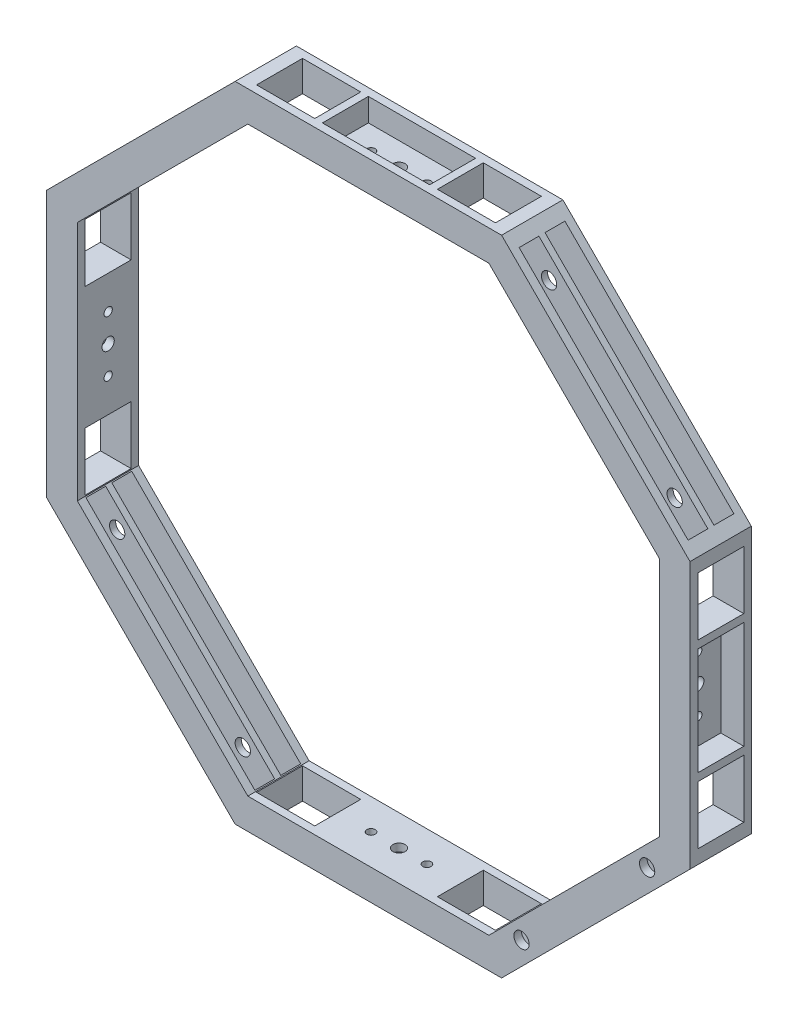
SolidWorks part; units mm, degrees
ref_plane "Plano frontal" through (0, 0, 0) normal (0, 0, 1) x (1, 0, 0)
ref_plane "Plano superior" through (0, 0, 0) normal (0, 1, 0) x (1, 0, 0)
ref_plane "Plano direito" through (0, 0, 0) normal (1, 0, 0) x (0, 0, -1)
sketch "Esboço1" plane through (0, 0, 0) normal (0, 0, 1) x (1, 0, 0)
  line L9 (210, 86.9848) -> (86.9848, 210)
  line L10 (86.9848, 210) -> (-86.9848, 210)
  line L11 (-86.9848, 210) -> (-210, 86.9848)
  line L12 (-210, 86.9848) -> (-210, -86.9848)
  line L13 (-210, -86.9848) -> (-86.9848, -210)
  line L14 (-86.9848, -210) -> (86.9848, -210)
  line L15 (86.9848, -210) -> (210, -86.9848)
  line L16 (210, -86.9848) -> (210, 86.9848)
  line L17 (190, 78.7006) -> (78.7006, 190)
  line L18 (78.7006, 190) -> (-78.7006, 190)
  line L19 (-78.7006, 190) -> (-190, 78.7006)
  line L20 (-190, 78.7006) -> (-190, -78.7006)
  line L21 (-190, -78.7006) -> (-78.7006, -190)
  line L22 (-78.7006, -190) -> (78.7006, -190)
  line L23 (78.7006, -190) -> (190, -78.7006)
  line L24 (190, -78.7006) -> (190, 78.7006)
  circle A0 centre (0, 0) radius 210 construction
  circle A1 centre (0, 0) radius 190 construction
extrude "Ressalto-extrusão1" add sketch "Esboço1" along normal blind 40
sketch "Esboço2" plane through (210, 0, 0) normal (1, 0, 0) x (0, 0, -1)
  line L1 (-4.9012, 78) -> (-4.9012, -78)
  line L23 (-4.9012, 78) -> (-34.9012, 78)
  line L24 (-34.9012, 78) -> (-34.9012, -78)
  line L25 (-4.9012, -78) -> (-34.9012, -78)
  line L26 (-4.9012, 78) -> (-4.9012, -78)
  line L27 (-4.9012, 78) -> (-34.9012, 78)
  line L28 (-34.9012, 78) -> (-34.9012, -78)
  line L29 (-4.9012, -78) -> (-34.9012, -78)
  line L30 (-4.9012, 0) -> (-4.9012, -40.0505)
  line L31 (-34.9012, 0) -> (-34.9012, -40.0505)
  line L32 (-4.9012, -40.0505) -> (-34.9012, -40.0505)
  line L33 (-4.9012, 0) -> (-4.9012, 40)
  line L34 (-34.9012, 0) -> (-34.9012, 40)
  line L35 (-4.9012, 40) -> (-34.9012, 40)
  line L36 (-4.9012, 35) -> (-4.9012, -35)
  line L37 (-4.9012, 35) -> (-34.9012, 35)
  line L38 (-34.9012, 35) -> (-34.9012, -35)
  line L39 (-4.9012, -35) -> (-34.9012, -35)
  circle A0 centre (-19.9012, 0) radius 4
  circle A1 centre (-19.9012, -18.25) radius 2.7
  circle A2 centre (-19.9012, 18.25) radius 2.7
extrude "Corte-extrusão2" cut sketch "Esboço2" against normal up to next and the other way through all contours L1 L32 L24 L25 | A0 | A2 | A1 | L35 L1 L23 L24 region at (210, 59, 19.9012) region at (210, -59.0253, 19.9012) region at (210, 0, 19.9012) region at (210, -18.25, 19.9012) region at (210, 18.25, 19.9012)
sketch "Esboço15" plane through (-148.4924, 148.4924, 0) normal (-0.7071, 0.7071, 0) x (0, 0, 1)
  line L0 (40, 86.9848) -> (0, 86.9848) construction
  line L1 (5, 86.9848) -> (35, 86.9848)
  line L2 (5, 86.9848) -> (5, -86.9848)
  line L3 (5, -86.9848) -> (35, -86.9848)
  line L4 (35, 86.9848) -> (35, -86.9848)
  line L5 (40, -86.9848) -> (0, -86.9848) construction
  line L9 (20, 86.9848) -> (22, 86.9848)
  line L11 (20, -86.9848) -> (22, -86.9848)
  line L12 (22, 78) -> (22, -78)
  line L14 (20, 86.9848) -> (18, 86.9848)
  line L16 (20, -86.9848) -> (18, -86.9848)
  line L17 (18, 78) -> (18, -78)
  line L19 (5, 86.9848) -> (35, 86.9848)
  line L20 (5, 86.9848) -> (5, 78)
  line L21 (5, 78) -> (35, 78)
  line L22 (35, 86.9848) -> (35, 78)
  line L24 (5, -86.9848) -> (35, -86.9848)
  line L25 (5, -86.9848) -> (5, -78)
  line L26 (5, -78) -> (35, -78)
  line L27 (35, -86.9848) -> (35, -78)
extrude "Corte-extrusão5" cut sketch "Esboço15" against normal up to next contours L12 L26 L4 L21 | L2 L26 L17 L21 region at (-148.4924, 148.4924, 11.5) region at (-148.4924, 148.4924, 28.5)
sketch "Esboço16" plane through (148.4924, 148.4924, 0) normal (0.7071, 0.7071, 0) x (0, 0, -1)
  line L0 (-40, 86.9848) -> (0, 86.9848) construction
  line L2 (-34.9012, -78) -> (-34.9012, 86.9848)
  line L3 (-34.9012, 86.9848) -> (-5, 86.9848)
  line L4 (-5, -86.8738) -> (-5, 86.9848)
  line L8 (-34.9012, -78) -> (-5, -78)
  line L9 (-5, -86.8738) -> (-5, -78)
  line L10 (-5, 86.9848) -> (-34.9012, 86.9848)
  line L11 (-5, 86.9848) -> (-5, 78)
  line L12 (-5, 78) -> (-34.9012, 78)
  line L13 (-34.9012, 86.9848) -> (-34.9012, 78)
  line L14 (-19.9506, 78) -> (-18, 78)
  line L16 (-20, -78) -> (-18, -78)
  line L17 (-18, 78) -> (-18, -78)
  line L18 (-20, -78) -> (-22, -78)
  line L20 (-19.9506, 78) -> (-22, 78)
  line L21 (-22, -78) -> (-22, 78)
  line L22 (-34.9012, -78) -> (-5, -78)
  line L23 (-34.9012, -78) -> (-34.9012, -86.8738)
  line L24 (-34.9012, -86.8738) -> (-5, -86.8738)
  line L25 (-5, -78) -> (-5, -86.8738)
extrude "Corte-extrusão6" cut sketch "Esboço16" against normal through all both and the other way through all contours L8 L21 L12 L2 | L12 L17 L8 L4 region at (148.4924, 148.4924, 28.4506) region at (148.4924, 148.4924, 11.5)
sketch "Esboço18" plane through (0, -210, 0) normal (0, -1, 0) x (1, 0, 0)
  line L1 (-78, 35) -> (78, 35)
  line L2 (-78, 35) -> (-78, 5)
  line L3 (-78, 5) -> (78, 5)
  line L4 (78, 35) -> (78, 5)
  line L5 (-78, 35) -> (78, 35)
  line L6 (-78, 35) -> (-78, 5)
  line L7 (-78, 5) -> (78, 5)
  line L8 (78, 35) -> (78, 5)
  line L9 (0, 35) -> (40.0505, 35)
  line L11 (0, 5) -> (40.0505, 5)
  line L12 (40.0505, 35) -> (40.0505, 5)
  line L13 (0, 35) -> (-40, 35)
  line L15 (0, 5) -> (-40, 5)
  line L16 (-40, 35) -> (-40, 5)
  line L17 (-35, 35) -> (35, 35)
  line L18 (-35, 35) -> (-35, 5)
  line L19 (-35, 5) -> (35, 5)
  line L20 (35, 35) -> (35, 5)
  circle A0 centre (0, 20) radius 4
  circle A1 centre (18.25, 20) radius 2.7
  circle A2 centre (-18.25, 20) radius 2.7
  line M8 (86.9848, 0) -> (86.9848, 40)
  line M12 (-86.9848, 40) -> (-86.9848, 0)
sketch "Esboço26" plane through (0, 0, 0) normal (0, 0, -1) x (-1, 0, 0)
  circle A0 centre (100, 182) radius 5
  circle A1 centre (182, 100) radius 5
  circle A2 centre (-182, -100) radius 5
  circle A3 centre (-100, -182) radius 5
  circle A4 centre (100, -182) radius 5
  circle A5 centre (182, -100) radius 5
  circle A6 centre (-182, 100) radius 5
  circle A7 centre (-100, 182) radius 5
  point P16 (0, 0)
extrude "Corte-extrusão10" cut sketch "Esboço26" against normal up to next from surface starting at face at (141.4214, 141.4214, 18)
extrude "Corte-extrusão12" cut sketch "Esboço18" against normal through all contours L16 L1 L3 M12 | L1 L12 L3 M8 | A2 | A0 | A1 region at (-59, -210, 20) region at (59.0253, -210, 20) region at (0, -210, 20) region at (18.25, -210, 20) region at (-18.25, -210, 20)
extrude "Corte-extrusão13" cut sketch "Esboço18<4>" against normal blind 15 contours L20 L5 L13 L18 L15 L7 A2 A1 A0 region at (-17.5, -210, 34.2384)
sketch "Esboço18<4>" plane through (0, -210, 0) normal (0, -1, 0) x (1, 0, 0) same geometry as "Esboço18"
extrude "Corte-extrusão14" cut sketch "Esboço2<5>" against normal blind 15 contours L39 L26 L33 L37 L34 L28 A2 A1 A0 region at (210, 17.5, 5.6628)
sketch "Esboço2<5>" plane through (210, 0, 0) normal (1, 0, 0) x (0, 0, -1) same geometry as "Esboço2"
mirror "Espelhar6" about plane through (0, 0, 0) normal (1, 0, 0) of "Corte-extrusão2", "Corte-extrusão14"
ref_plane "Plano1" through (0, 0, 0) normal (-0.7071, 0.7071, 0) x (0.7071, 0.7071, 0)
mirror "Espelhar8" about plane through (0, 0, 0) normal (-0.7071, 0.7071, 0) of "Corte-extrusão5"
mirror "Espelhar9" about plane through (0, 0, 0) normal (0, 1, 0) of "Corte-extrusão13", "Corte-extrusão12"
